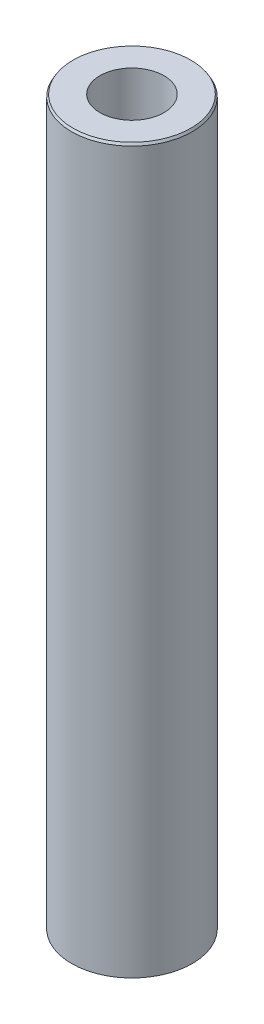
SolidWorks part; units mm, degrees
ref_plane "Front Plane" through (0, 0, 0) normal (0, 0, 1) x (1, 0, 0)
ref_plane "Top Plane" through (0, 0, 0) normal (0, 1, 0) x (1, 0, 0)
ref_plane "Right Plane" through (0, 0, 0) normal (1, 0, 0) x (0, 0, -1)
sketch "Sketch1" plane through (0, 0, 0) normal (0, 1, 0) x (1, 0, 0)
  circle A0 centre (0, 0) radius 50
  dimension "SHAFT_OD" = 100
extrude "Boss-Extrude1" add sketch "Sketch1" along normal blind 600
sketch "Sketch2" plane through (0, 0, 0) normal (0, 1, 0) x (1, 0, 0)
  circle A0 centre (0, 0) radius 26.5466
  dimension "BORE_D" = 53.0932
extrude "Cut-Extrude1" cut sketch "Sketch2" along normal through all
chamfer "Chamfer1" distance 1.97 angle 30 2 edges at (0, 600, 50) (0, 0, 50) first distance on face at (0, 600, 50) first distance on face at (0, 0, 26.5466)
